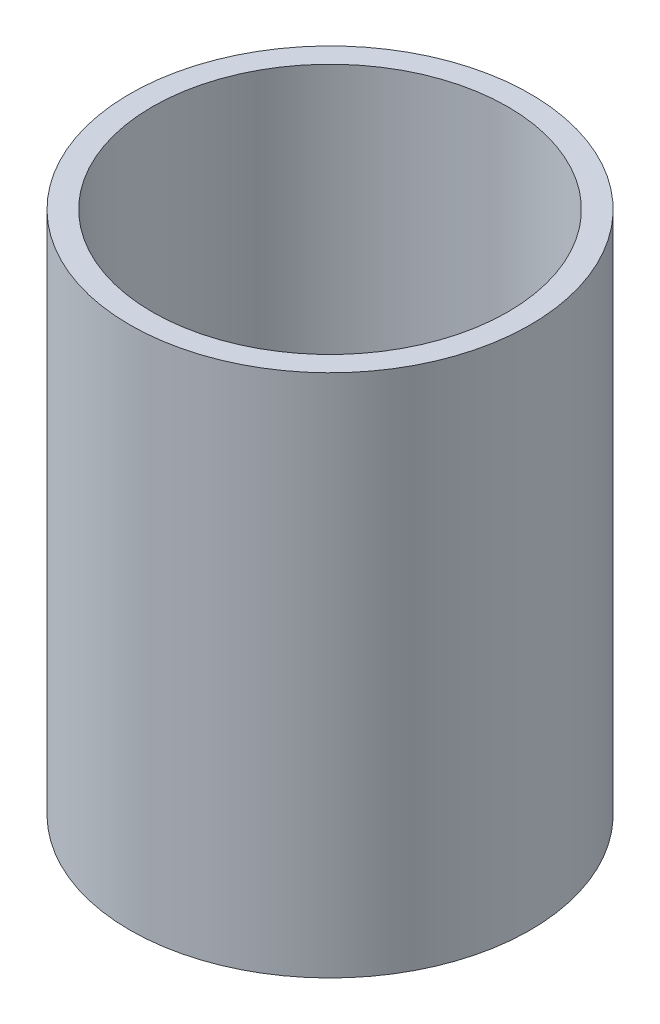
SolidWorks part; units mm, degrees
ref_plane "Front Plane" through (0, 0, 0) normal (0, 0, 1) x (1, 0, 0)
ref_plane "Top Plane" through (0, 0, 0) normal (0, 1, 0) x (1, 0, 0)
ref_plane "Right Plane" through (0, 0, 0) normal (1, 0, 0) x (0, 0, -1)
sketch "Sketch1" plane through (0, 0, 0) normal (0, 1, 0) x (1, 0, 0)
  circle A0 centre (0, 0) radius 40
  dimension "SLEEVE_OD" = 80
extrude "Boss-Extrude1" add sketch "Sketch1" along normal blind 104.7406
sketch "Sketch2" plane through (0, 0, 0) normal (0, 1, 0) x (1, 0, 0)
  circle A0 centre (0, 0) radius 35.5257
  dimension "BORE_D" = 71.0513
extrude "Cut-Extrude1" cut sketch "Sketch2" along normal through all
chamfer "Chamfer1" distance 3.7435 angle 30 rebuild error yes
